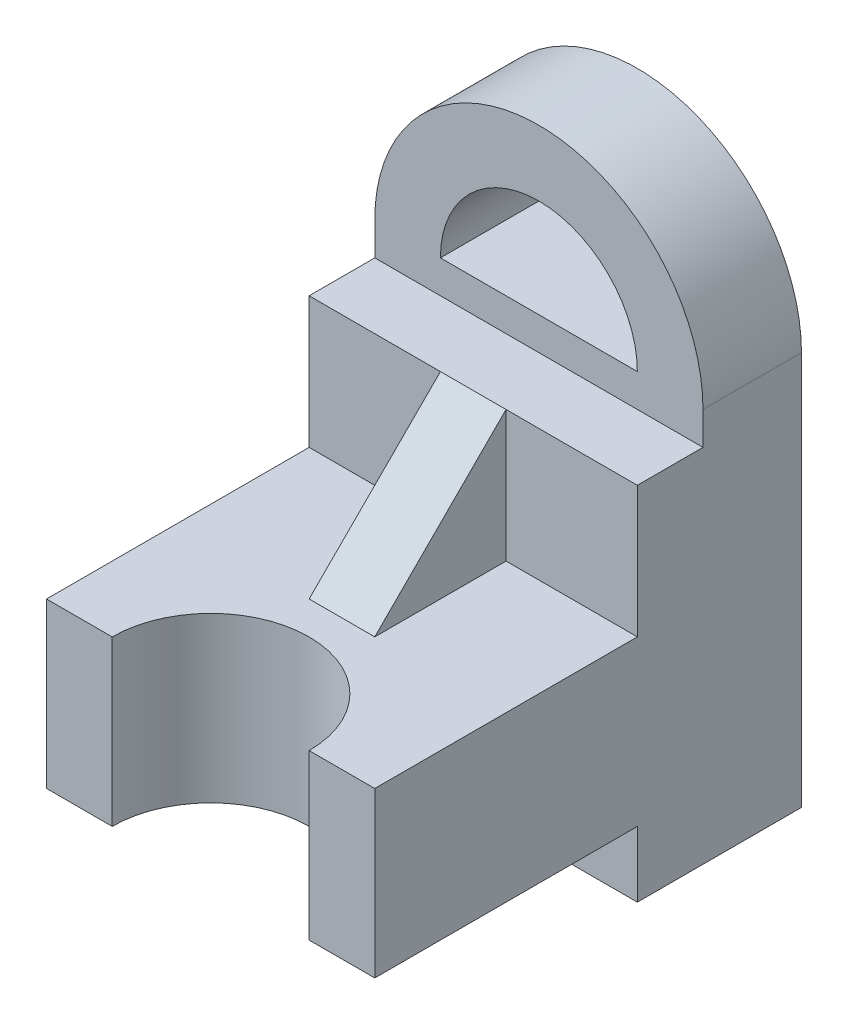
SolidWorks part; units mm, degrees
ref_plane "Front Plane" through (0, 0, 0) normal (0, 0, 1) x (1, 0, 0)
ref_plane "Top Plane" through (0, 0, 0) normal (0, 1, 0) x (1, 0, 0)
ref_plane "Right Plane" through (0, 0, 0) normal (1, 0, 0) x (0, 0, -1)
sketch "Sketch3" plane through (0, 0, 0) normal (0, 0, 1) x (1, 0, 0)
  line L0 (25, 0) -> (-25, 0)
  line L1 (-25, 0) -> (-25, 20)
  line L2 (-25, 20) -> (25, 20)
  line L3 (25, 20) -> (25, 0)
  line L4 (-25, 0) -> (-25, -25)
  line L5 (-25, -25) -> (25, -25)
  line L6 (25, -25) -> (25, 0)
  line L7 (-25, -25) -> (-25, -35)
  line L8 (-25, -35) -> (25, -35)
  line L9 (25, -35) -> (25, -25)
  line L10 (25, -25) -> (-25, -25)
  line L11 (-25, 20) -> (-25, 25)
  line L12 (-25, 25) -> (-25, 20)
  line L13 (25, 25) -> (25, 20)
  line L14 (15, 25) -> (-15, 25)
  line L15 (25, 25) -> (25, 20)
  line L16 (-25, 20) -> (25, 20)
  arc A1 (-25, 25) -> (25, 25) centre (0, 25) cw
  arc A2 (-15, 25) -> (15, 25) centre (0, 25) cw
  point P4 (0, 0)
  point P14 (0, 20)
  point P15 (0, 50)
  point P19 (0, 25)
  dimension "D4" = 25
  dimension "D7" = 15
  dimension "D1" = 20
  dimension "D2" = 25
  dimension "D3" = 10
  dimension "D5" = 50
  dimension "D6" = 30
extrude "Boss-Extrude1" add sketch "Sketch3" along normal blind 15 contours A1 L11 L2 L13 L14 A2 region at (0, 20.5831, 0)
extrude "Boss-Extrude2" add sketch "Sketch3<3>" along normal blind 25 contours L3 L2 L1 L0 region at (0, 10, 0)
sketch "Sketch3<3>" plane through (0, 0, 0) normal (0, 0, 1) x (1, 0, 0) same geometry as "Sketch3"
extrude "Boss-Extrude3" add sketch "Sketch3<4>" along normal blind 65 contours L5 L6 L0 L4 region at (0, -12.5, 0)
sketch "Sketch3<4>" plane through (0, 0, 0) normal (0, 0, 1) x (1, 0, 0) same geometry as "Sketch3"
extrude "Boss-Extrude4" add sketch "Sketch3<6>" along normal blind 25 contours L8 L9 L5 L7 region at (0, -30, 0)
sketch "Sketch3<6>" plane through (0, 0, 0) normal (0, 0, 1) x (1, 0, 0) same geometry as "Sketch3"
sketch "Sketch5" plane through (0, 0, 0) normal (0, 1, 0) x (1, 0, 0)
  line L0 (25, -65) -> (-25, -65) construction
  line L1 (-15, -65) -> (15, -65)
  arc A0 (-15, -65) -> (15, -65) centre (0, -65) cw
  dimension "D1" = 30
extrude "Cut-Extrude1" cut sketch "Sketch5" against normal through all both and the other way through all
sketch "Sketch6" plane through (0, 0, 0) normal (1, 0, 0) x (0, 0, -1)
  line L0 (-25, 20) -> (-45, 0)
  line L1 (-65, 0) -> (-25, 0) construction
  line L2 (-45, 0) -> (-25, 0)
  line L3 (-25, 0) -> (-25, 20)
  dimension "D1" = 20
extrude "Boss-Extrude5" add sketch "Sketch6" along normal mid plane 10
